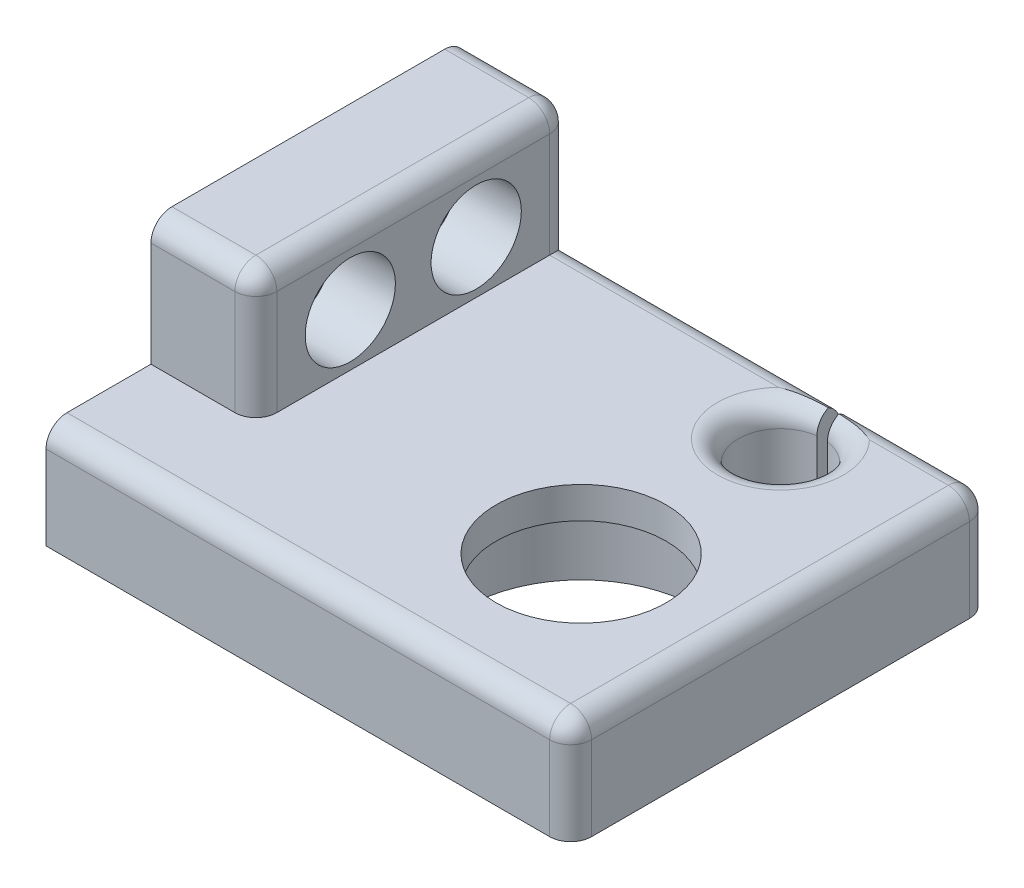
SolidWorks part; units mm, degrees
ref_plane "Front Plane" through (0, 0, 0) normal (0, 0, 1) x (1, 0, 0)
ref_plane "Top Plane" through (0, 0, 0) normal (0, 1, 0) x (1, 0, 0)
ref_plane "Right Plane" through (0, 0, 0) normal (1, 0, 0) x (0, 0, -1)
sketch "Sketch2" plane through (0, 0, 0) normal (0, 1, 0) x (1, 0, 0)
  line L0 (36.15, -6.15) -> (36.15, -25.15) construction
  line L1 (0, 0) -> (50, 0)
  line L2 (0, 0) -> (0, -40)
  line L3 (0, -40) -> (50, -40)
  line L4 (50, 0) -> (50, -40)
  line L5 (36.15, -2.1814) -> (36.15, -6.15) construction
  line L6 (35.65, 0) -> (36.65, 0)
  line L7 (35.65, 0) -> (35.65, -2.1814)
  line L8 (35.65, -2.1814) -> (36.65, -2.1814)
  line L9 (36.65, 0) -> (36.65, -2.1814)
  line L10 (36.15, -25.15) -> (36.15, -33.2346) construction
  line L12 (35.65, -40) -> (36.65, -40)
  line L13 (35.65, -40) -> (35.65, -33.2346) construction
  line L14 (35.65, -33.2346) -> (36.65, -33.2346)
  line L15 (36.65, -40) -> (36.65, -33.2346) construction
  circle A2 centre (36.15, -6.15) radius 4
  circle A3 centre (36.15, -25.15) radius 11.1 construction
  circle A4 centre (36.15, -25.15) radius 8.1
  dimension "D3" = 13.85
  dimension "D4" = 6.15
  dimension "D5" = 19
  dimension "D6" = 50
  dimension "D7" = 40
  dimension "D8" = 1
  dimension "D1" = 22.2
  dimension "D2" = 8
  dimension "D9" = 3
  dimension "D10" = 1
extrude "Boss-Extrude1" add sketch "Sketch2" along normal blind 10 contours L4 L1 L2 L3 A2 region at (23.3446, 0, 19.8137)
sketch "Sketch3" plane through (0, 0, 0) normal (0, -1, 0) x (1, 0, 0)
  circle A0 centre (36.15, 25.15) radius 11.1 construction
  circle A1 centre (36.15, 25.15) radius 11.1
  circle A2 centre (36.15, 25.15) radius 8.1
  circle A3 centre (36.15, 25.15) radius 8.1 construction
extrude "Cut-Extrude1" cut sketch "Sketch3" against normal blind 7
sketch "Sketch10" plane through (0, 0, 0) normal (0, 0, -1) x (-1, 0, 0)
  line L1 (0, 10) -> (-10, 10)
  line L2 (0, 10) -> (0, 22)
  line L3 (0, 22) -> (-10, 22)
  line L4 (-10, 10) -> (-10, 22)
  dimension "D1" = 12
  dimension "D2" = 10
extrude "Boss-Extrude5" add sketch "Sketch10" against normal blind 30
sketch "Sketch11" plane through (10, 0, 0) normal (1, 0, 0) x (0, 0, -1)
  line L0 (-21, 15) -> (-9, 15) construction
  line L1 (-9, 15) -> (0, 15) construction
  line L3 (-21, 15) -> (-30, 15) construction
  line L5 (0, 22) -> (0, 10) construction
  line L6 (-30, 22) -> (-30, 10) construction
  line L7 (0, 10) -> (-40, 10) construction
  circle A0 centre (-21, 15) radius 2.8
  circle A1 centre (-9, 15) radius 2.8
  point P4 (0, 0)
  point P6 (0, 13.1683)
  point P9 (0, 0)
  point P11 (-30, 13.1683)
  dimension "D1" = 12
  dimension "D2" = 5.6
  dimension "D3" = 5
extrude "Cut-Extrude4" cut sketch "Sketch11" against normal through all
sketch "Sketch12" plane through (10, 0, 0) normal (1, 0, 0) x (0, 0, -1)
  circle A0 centre (-21, 15) radius 4.3
  circle A1 centre (-9, 15) radius 4.3
  dimension "D1" = 8.6
extrude "Cut-Extrude5" cut sketch "Sketch12" against normal blind 6
fillet "Fillet2" radius 2 12 edges at (22.825, 10, 0) (43.325, 10, 0) (5, 22, 0) (10, 16, 0) (10, 22, 15) (5, 22, 30) (10, 16, 30) (25, 10, 40) (50, 10, 20) (50, 5, 40) (50, 5, 0) (36.15, 10, 10.15)
